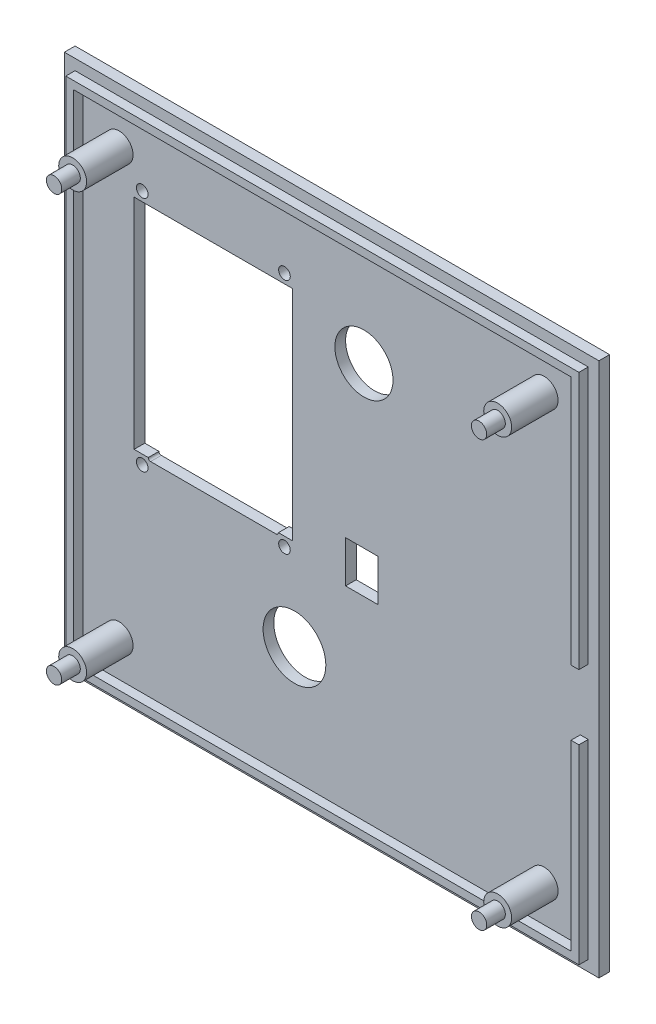
SolidWorks part; units mm, degrees
ref_plane "Front Plane" through (0, 0, 0) normal (0, 0, 1) x (1, 0, 0)
ref_plane "Top Plane" through (0, 0, 0) normal (0, 1, 0) x (1, 0, 0)
ref_plane "Right Plane" through (0, 0, 0) normal (1, 0, 0) x (0, 0, -1)
sketch "Sketch1" plane through (0, 0, 0) normal (0, 0, 1) x (1, 0, 0)
  line L1 (-55.2, 55.2) -> (55.2, 55.2)
  line L2 (-55.2, 55.2) -> (-55.2, -55.2)
  line L3 (-55.2, -55.2) -> (55.2, -55.2)
  line L4 (55.2, 55.2) -> (55.2, -55.2)
  line L5 (-55.2, 55.2) -> (55.2, -55.2) construction
  line L6 (-55.2, -55.2) -> (55.2, 55.2) construction
  line L7 (-53.5, 53.5) -> (53.5, 53.5)
  line L8 (-53.5, 53.5) -> (-53.5, -53.5)
  line L9 (-53.5, -53.5) -> (53.5, -53.5)
  line L10 (53.5, 53.5) -> (53.5, -53.5)
  line L11 (-53.5, 53.5) -> (53.5, -53.5) construction
  line L12 (-53.5, -53.5) -> (53.5, 53.5) construction
  point P0 (0, 0)
  point P5 (0, 0)
  dimension "D1" = 1.7
  dimension "D2" = 1.7
  dimension "D3" = 107
extrude "Boss-Extrude1" add sketch "Sketch1" along normal blind 2
sketch "Sketch3" plane through (0, 0, 0) normal (0, 0, -1) x (-1, 0, 0)
  line L1 (-57.5, 57.5) -> (57.5, 57.5)
  line L2 (-57.5, 57.5) -> (-57.5, -57.5)
  line L3 (-57.5, -57.5) -> (57.5, -57.5)
  line L4 (57.5, 57.5) -> (57.5, -57.5)
  line L5 (-57.5, 57.5) -> (57.5, -57.5) construction
  line L6 (-57.5, -57.5) -> (57.5, 57.5) construction
  point P0 (0, 0)
  dimension "D1" = 115
  dimension "D2" = 115
extrude "Boss-Extrude2" add sketch "Sketch3" along normal blind 2.3
sketch "Sketch4" plane through (0, 0, 0) normal (0, 0, 1) x (1, 0, 0)
  line L5 (-45.72, 45.72) -> (45.72, 45.72) construction
  line L6 (-45.72, 45.72) -> (-45.72, -45.72) construction
  line L7 (-45.72, -45.72) -> (45.72, -45.72) construction
  line L8 (45.72, 45.72) -> (45.72, -45.72) construction
  line L9 (-45.72, 45.72) -> (45.72, -45.72) construction
  line L10 (-45.72, -45.72) -> (45.72, 45.72) construction
  circle A4 centre (-45.72, 45.72) radius 3
  circle A5 centre (45.72, 45.72) radius 3
  circle A6 centre (45.72, -45.72) radius 3
  circle A7 centre (-45.72, -45.72) radius 3
  point P0 (0, 0)
  dimension "D3" = 6
  dimension "D4" = 6
  dimension "D5" = 6
  dimension "D6" = 6
  dimension "D1" = 91.44
  dimension "D2" = 91.44
extrude "Boss-Extrude3" add sketch "Sketch4" along normal blind 10
sketch "Sketch5" plane through (0, 0, 0) normal (0, 0, 1) x (1, 0, 0)
  line L0 (3, -7.2) -> (10, -7.2) construction
  line L49 (-50, 50) -> (50, 50) construction
  line L51 (-50, 50) -> (-50, -50) construction
  line L52 (-50, -50) -> (50, -50) construction
  line L53 (50, 50) -> (50, -50) construction
  line L54 (-50, 50) -> (50, -50) construction
  line L55 (-50, -50) -> (50, 50) construction
  line L56 (3, -11.7) -> (10, -11.7)
  line L57 (3, -11.7) -> (3, -2.7)
  line L58 (3, -2.7) -> (10, -2.7)
  line L59 (10, -11.7) -> (10, -2.7)
  line L60 (-25.45, -9) -> (-25.45, 38) construction
  line L61 (-42.5, -9) -> (-8.4, -9)
  line L62 (-42.5, -9) -> (-42.5, 38)
  line L63 (-42.5, 38) -> (-8.4, 38)
  line L64 (-8.4, -9) -> (-8.4, 38)
  line L65 (6.5, -11.7) -> (6.5, -2.7) construction
  line L66 (-43, -13.5) -> (-7.9, -13.5) construction
  line L67 (-43, -13.5) -> (-43, 42.5) construction
  line L68 (-43, 42.5) -> (-7.9, 42.5) construction
  line L69 (-7.9, -13.5) -> (-7.9, 42.5) construction
  line L70 (-43, -13.5) -> (-7.9, 42.5) construction
  line L71 (-43, 42.5) -> (-7.9, -13.5) construction
  line L76 (-39.45, -8.5) -> (-11.45, -8.5)
  line L77 (-39.45, -8.5) -> (-39.45, -9.5)
  line L78 (-39.45, -9.5) -> (-11.45, -9.5)
  line L79 (-11.45, -8.5) -> (-11.45, -9.5)
  line L80 (-39.45, -8.5) -> (-11.45, -9.5) construction
  line L81 (-39.45, -9.5) -> (-11.45, -8.5) construction
  circle A2 centre (-8, -28.6) radius 6.75
  circle A3 centre (6.95, 31.72) radius 6.25
  circle A4 centre (-40.75, -11) radius 1.25
  circle A5 centre (-10.15, -11) radius 1.25
  circle A6 centre (-10.15, 40) radius 1.25
  circle A7 centre (-40.75, 40) radius 1.25
  point P0 (0, 0)
  point P11 (6.5, -7.2)
  point P23 (-25.45, 14.5)
  dimension "D11" = 18.28
  dimension "D3" = 42
  dimension "D4" = 13.5
  dimension "D10" = 12.5
  dimension "D17" = 2.5
  dimension "D1" = 100
  dimension "D2" = 100
  dimension "D5" = 21.4
  dimension "D6" = 7
  dimension "D7" = 9
  dimension "D8" = 43.5
  dimension "D9" = 42.8
  dimension "D12" = 43.05
  dimension "D13" = 34.1
  dimension "D14" = 47
  dimension "D15" = 56
  dimension "D16" = 35.1
  dimension "D18" = 2.25
  dimension "D19" = 2.5
  dimension "D22" = 7.5
  dimension "D23" = 7.5
  dimension "D24" = 28
  dimension "D25" = 1
  dimension "D20" = 2
  dimension "D21" = 2
extrude "Cut-Extrude2" cut sketch "Sketch5" against normal through all both and the other way through all contours L61 L64 L63 L62 | A6 | A7 | A4 | A5 | L56 L59 L58 L57 | A3 | A2 | L79 L76 L77 L63 | L79 L63 L77 L78 region at (6.5, -7.2, 0) region at (-25.45, 14.7049, 0) region at (-25.45, -8.75, 0) region at (-25.45, -9.25, 0) region at (-8, -28.6, 0) region at (6.95, 31.72, 0) region at (-40.75, -11, 0) region at (-10.15, -11, 0) region at (-10.15, 40, 0) region at (-40.75, 40, 0)
sketch "Sketch6" plane through (0, 0, 10) normal (0, 0, 1) x (1, 0, 0)
  circle A4 centre (-45.72, 45.72) radius 1.65
  circle A5 centre (45.72, 45.72) radius 1.65
  circle A6 centre (45.72, -45.72) radius 1.65
  circle A7 centre (-45.72, -45.72) radius 1.65
  dimension "D1" = 3.3
  dimension "D2" = 3.3
  dimension "D3" = 3.3
  dimension "D4" = 3.3
extrude "Boss-Extrude4" add sketch "Sketch6" along normal blind 4
sketch "Sketch7" plane through (0, 0, 0) normal (0, 0, 1) x (1, 0, 0)
  line L0 (10, -7.2) -> (57.5, -7.2) construction
  line L1 (10, -2.7) -> (10, -11.7) construction
  line L2 (57.5, 57.5) -> (57.5, -57.5) construction
  line L4 (45.4265, -0.2) -> (69.5735, -0.2)
  line L5 (45.4265, -0.2) -> (45.4265, -14.2)
  line L6 (45.4265, -14.2) -> (69.5735, -14.2)
  line L7 (69.5735, -0.2) -> (69.5735, -14.2)
  line L8 (45.4265, -0.2) -> (69.5735, -14.2) construction
  line L9 (45.4265, -14.2) -> (69.5735, -0.2) construction
  dimension "D1" = 14
extrude "Cut-Extrude4" cut sketch "Sketch7" along normal blind 10
fillet "Fillet1" radius 0.5 2 edges at (-11.45, -9.5, -1.15) (-39.45, -9.5, -1.15)
